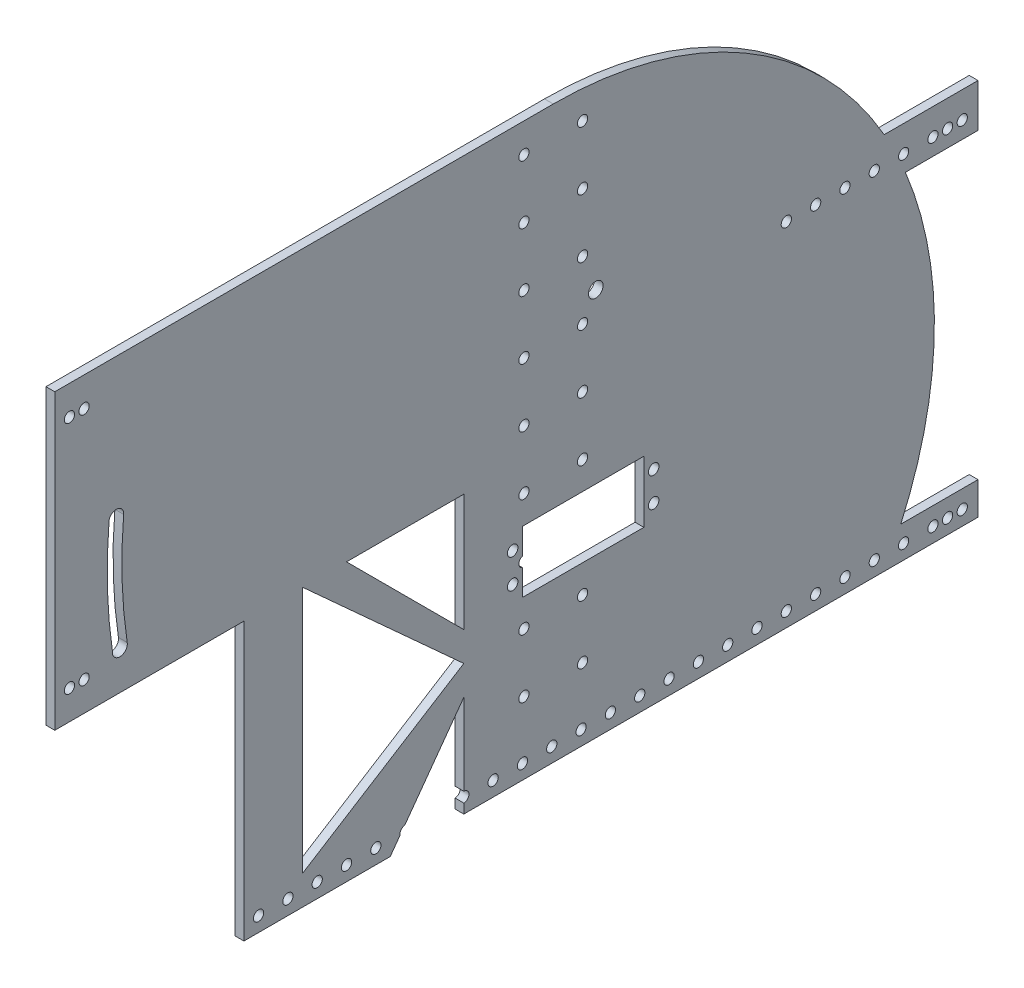
SolidWorks part; units mm, degrees
ref_plane "Front Plane" through (0, 0, 0) normal (0, 0, 1) x (1, 0, 0)
ref_plane "Top Plane" through (0, 0, 0) normal (0, 1, 0) x (1, 0, 0)
ref_plane "Right Plane" through (0, 0, 0) normal (1, 0, 0) x (0, 0, -1)
sketch "Sketch1" plane through (0, 0, 0) normal (1, 0, 0) x (0, 0, -1)
  line L0 (0, 130) -> (-170, 130)
  line L1 (-170, 130) -> (-170, 30)
  line L2 (-170, 30) -> (-126.4911, 30)
  arc A0 (-126.4911, 30) -> (0, 130) centre (0, 0) ccw
  circle A1 centre (0, 0) radius 5
  dimension "D1" = 260
  dimension "D2" = 10
  dimension "D3" = 100
  dimension "D4" = 170
extrude "Boss-Extrude1" add sketch "Sketch1" along normal blind 3
sketch "Sketch2" plane through (3, 0, 0) normal (1, 0, 0) x (0, 0, -1)
  line L0 (-10, 10) -> (-10, -10) construction
  line L1 (-10, -10) -> (30.4, -10) construction
  line L2 (30.4, -10) -> (30.4, 10) construction
  line L3 (30.4, 10) -> (-10, 10) construction
  line L4 (30.9, 10.5) -> (-10.5, 10.5)
  line L5 (-10.5, 10.5) -> (-10.5, -10.5)
  line L6 (-10.5, -10.5) -> (30.9, -10.5)
  line L7 (30.9, -10.5) -> (30.9, 10.5)
  circle A1 centre (0, 0) radius 5 construction
  circle A2 centre (-13.85, 5) radius 1.8
  circle A3 centre (-13.85, -5) radius 1.8
  circle A4 centre (34.25, 5) radius 1.8
  circle A5 centre (34.25, -5) radius 1.8
  point P11 (-10, 0)
  dimension "D1" = 10
  dimension "D2" = 10
  dimension "D4" = 3.6
  dimension "D7" = 3.85
  dimension "D8" = 5
  dimension "D10" = 5
  dimension "D12" = 3.85
  dimension "D13" = 10
  dimension "D3" = 40.4
  dimension "D5" = 20
  dimension "D9" = 10
  dimension "D11" = 3.85
  dimension "D6" = 0.5
extrude "ServoHole" cut sketch "Sketch2" against normal through all
sketch "Sketch3" plane through (3, 0, 0) normal (1, 0, 0) x (0, 0, -1)
  line L1 (123.9473, -130) -> (-198.7557, -130)
  line L2 (123.9473, -130) -> (123.9473, -64.5)
  line L3 (123.9473, -64.5) -> (-198.7557, -64.5)
  line L4 (-198.7557, -130) -> (-198.7557, -64.5)
  arc A0 (-126.4911, 30) -> (0, 130) centre (0, 0) ccw construction
  dimension "D1" = 130
  dimension "D2" = 64.5
extrude "Cut-Extrude2" cut sketch "Sketch3" against normal through all
sketch "Sketch4" plane through (3, 0, 0) normal (1, 0, 0) x (0, 0, -1)
  line L1 (-170, 30) -> (-105.5, 30)
  line L2 (-170, 30) -> (-170, -85)
  line L3 (-170, -85) -> (-105.5, -85)
  line L4 (-30.5, 30) -> (-30.5, -10)
  line L5 (-10.5, 10.5) -> (-10.5, -10.5) construction
  line L6 (-70.5, 30) -> (-30.5, -10)
  line L7 (-85.5, 30) -> (-30.5, -20)
  line L8 (-30.5, -20) -> (-85.5, -54.5)
  line L9 (-30.5, -30) -> (-70.5, -85)
  line L10 (-70.5, 30) -> (-30.5, 30)
  line L11 (-30.5, -30) -> (-30.5, -85)
  line L12 (-70.5, -85) -> (-30.5, -85)
  line L13 (-85.5, 30) -> (-85.5, -54.5)
  line L14 (-105.5, 30) -> (-105.5, -85)
  line L15 (112.8705, -64.5) -> (-112.8705, -64.5) construction
  dimension "D1" = 20
  dimension "D2" = 40
  dimension "D3" = 45
  dimension "D4" = 10
  dimension "D5" = 10
  dimension "D6" = 15
  dimension "D7" = 20
  dimension "D8" = 40
  dimension "D9" = 20
  dimension "D10" = 10
  dimension "D11" = 115
extrude "Cut-Extrude5" cut sketch "Sketch4" against normal through all
sketch "Sketch5" plane through (3, 0, 0) normal (1, 0, 0) x (0, 0, -1)
  line L0 (112.8705, -64.5) -> (-30.5, -64.5) construction
  line L1 (-30.5, -64.5) -> (-30.5, -30) construction
  circle A0 centre (-20.5, -59.5) radius 1.75
  dimension "D1" = 3.5
  dimension "D2" = 5
  dimension "D3" = 10
extrude "Cut-Extrude6" cut sketch "Sketch5" against normal blind 10
pattern_linear "LPattern1" count 14 spacing 10 along (0, 0, -1) of "Cut-Extrude6"
pattern_linear "LPattern2" count 14 spacing 10 along (0, 0, 1) of "Cut-Extrude6"
sketch "Sketch6" plane through (3, 0, 0) normal (1, 0, 0) x (0, 0, -1)
  circle A0 centre (109.5, 55.5) radius 1.75
  circle A1 centre (109.5, -59.5) radius 1.75 construction
  circle A2 centre (99.5, -59.5) radius 1.75 construction
  circle A3 centre (99.5, 55.5) radius 1.75
  circle A4 centre (89.5, 55.5) radius 1.75
  circle A5 centre (79.5, 55.5) radius 1.75
  dimension "D1" = 3.5
  dimension "D2" = 115
  dimension "D3" = 10
  dimension "D5" = 10
  dimension "D4" = 4
extrude "Cut-Extrude7" cut sketch "Sketch6" against normal blind 10
sketch "Sketch7" plane through (3, 0, 0) normal (1, 0, 0) x (0, 0, -1)
  line L0 (112.8705, -64.5) -> (144.8705, -64.5)
  line L1 (144.8705, -64.5) -> (144.8705, -53.383)
  line L2 (144.8705, -53.383) -> (118.5338, -53.383)
  line L3 (112.8705, 64.5) -> (144.8705, 64.5)
  line L4 (144.8705, 64.5) -> (144.8705, 49.7546)
  line L5 (144.8705, 49.7546) -> (120.102, 49.7546)
  arc A0 (112.8705, -64.5) -> (0, 130) centre (0, 0) ccw construction
  arc A1 (112.8705, -64.5) -> (118.5338, -53.383) centre (0, 0) ccw
  arc A2 (120.102, 49.7546) -> (112.8705, 64.5) centre (0, 0) ccw
  circle A3 centre (109.5, -59.5) radius 1.75 construction
  circle A4 centre (109.5, 55.5) radius 1.75 construction
  circle A5 centre (109.5, -59.5) radius 1.75 construction
  circle A6 centre (109.5, 55.5) radius 1.75 construction
  circle A7 centre (119.5, 55.5) radius 1.75
  circle A8 centre (129.5, 55.5) radius 1.75
  circle A9 centre (139.5, 55.5) radius 1.75
  circle A11 centre (119.5, -59.5) radius 1.75
  circle A12 centre (129.5, -59.5) radius 1.75
  circle A13 centre (139.5, -59.5) radius 1.75
  circle A15 centre (149.5, 55.5) radius 1.75 [skipped]
  circle A16 centre (149.5, -59.5) radius 1.75 [skipped]
  circle A17 centre (134.5, -59.5) radius 1.75
  circle A18 centre (134.5, 55.5) radius 1.75
  dimension "D4" = 10
  dimension "D6" = 5
  dimension "D8" = 10
  dimension "D10" = 5
  dimension "D3" = 32
  dimension "D7" = 32
  dimension "D1" = 5
  dimension "D2" = 5
  dimension "D5" = 2
  dimension "D9" = 2
extrude "Boss-Extrude2" add sketch "Sketch7" against normal blind 3
sketch "Sketch8" plane through (0, 0, 0) normal (-1, 0, 0) x (0, 0, 1)
  circle A0 centre (-14.5, 67.89) radius 2.5
  circle A1 centre (-79.5, 55.5) radius 1.75 construction
  arc A2 (146.5155, 82.0337) -> (145.2961, 43.5745) centre (-14.5, 67.89) cw
  arc A3 (151.5342, 82.0337) -> (150.3519, 43.5745) centre (-14.5, 67.89) cw
  arc A4 (145.2961, 43.5745) -> (150.3519, 43.5745) centre (147.824, 43.1898) ccw
  arc A5 (146.5155, 82.0337) -> (151.5342, 82.0337) centre (149.0248, 82.2541) cw
  point P10 (150.2639, 42.9853)
  point P11 (0, 0)
  dimension "D1" = 5
  dimension "D2" = 65
  dimension "D3" = 12.39
  dimension "D4" = 5
extrude "Cut-Extrude8" cut sketch "Sketch8" against normal blind 3
sketch "Sketch9" plane through (0, 0, 0) normal (-1, 0, 0) x (0, 0, 1)
  line L0 (0, 130) -> (170, 130) construction
  line L1 (170, 130) -> (170, 30) construction
  line L2 (170, 30) -> (105.5, 30) construction
  circle A0 centre (160, 40) radius 1.75
  circle A2 centre (160, 120) radius 1.75
  circle A4 centre (165, 40) radius 1.75
  circle A5 centre (165, 120) radius 1.75
  dimension "D1" = 3.5
  dimension "D2" = 10
  dimension "D3" = 10
  dimension "D4" = 10
  dimension "D5" = 10
  dimension "D6" = 2
extrude "Cut-Extrude9" cut sketch "Sketch9" against normal blind 10
sketch "Sketch10" plane through (0, 0, 0) normal (-1, 0, 0) x (0, 0, 1)
  line L0 (-144.8705, -64.5) -> (30.5, -64.5) construction
  line L4 (0, 130) -> (0, -64.5) construction
  line L5 (170, 130) -> (170, 30) construction
  line L6 (0, 130) -> (170, 130) construction
  circle A0 centre (10, 120) radius 1.75
  circle A2 centre (10, 100) radius 1.75
  circle A3 centre (10, 80) radius 1.75
  circle A4 centre (10, 60) radius 1.75
  circle A5 centre (10, 40) radius 1.75
  circle A6 centre (10, 20) radius 1.75
  circle A7 centre (10, 0) radius 1.75
  circle A8 centre (10, -20) radius 1.75
  circle A9 centre (10, -40) radius 1.75
  circle A10 centre (-10, 20) radius 1.75
  circle A11 centre (-10, -20) radius 1.75
  circle A12 centre (-10, -40) radius 1.75
  circle A13 centre (-10, 40) radius 1.75
  circle A14 centre (-10, 60) radius 1.75
  circle A15 centre (-10, 80) radius 1.75
  circle A16 centre (-10, 100) radius 1.75
  circle A17 centre (-10, 120) radius 1.75
  dimension "D2" = 10
  dimension "D3" = 10
  dimension "D4" = 3.5
  dimension "D6" = 20
  dimension "D1" = 170
  dimension "D5" = 9
extrude "Cut-Extrude10" cut sketch "Sketch10" against normal blind 10
sketch "Sketch11" plane through (0, 0, 0) normal (-1, 0, 0) x (0, 0, 1)
  line L0 (-144.8705, -64.5) -> (30.5, -64.5) construction
  line L1 (170, 130) -> (0, 130)
  line L2 (170, 130) -> (170, -64.5)
  line L3 (170, -64.5) -> (0, -64.5)
  line L4 (0, 130) -> (0, -64.5)
  dimension "D1" = 170
extrude "Cut-Extrude11" [suppressed] cut sketch "Sketch11" against normal blind 10
sketch "Sketch12" plane through (0, 0, 0) normal (-1, 0, 0) x (0, 0, 1)
  line L0 (0, 130) -> (170, 130) construction
  line L1 (-144.8705, -64.5) -> (0, -64.5)
  line L2 (-144.8705, -64.5) -> (-144.8705, 130)
  line L3 (-144.8705, 130) -> (0, 130)
  line L4 (0, -64.5) -> (0, 130)
  line L5 (170, 130) -> (170, 30) construction
  dimension "D1" = 170
extrude "Cut-Extrude12" [suppressed] cut sketch "Sketch12" against normal blind 10
